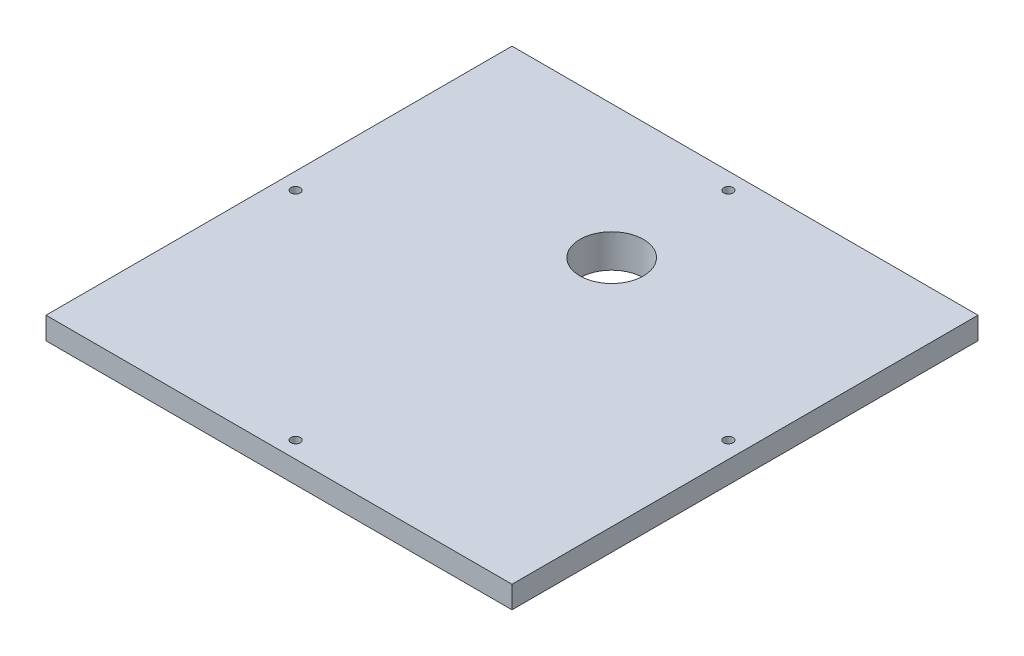
SolidWorks part; units mm, degrees
ref_plane "Front Plane" through (0, 0, 0) normal (0, 0, 1) x (1, 0, 0)
ref_plane "Top Plane" through (0, 0, 0) normal (0, 1, 0) x (1, 0, 0)
ref_plane "Right Plane" through (0, 0, 0) normal (1, 0, 0) x (0, 0, -1)
sketch "Sketch2" plane through (0, 0, 0) normal (0, 1, 0) x (1, 0, 0)
  line L1 (-105, -105) -> (105, -105)
  line L2 (-105, -105) -> (-105, 105)
  line L3 (-105, 105) -> (105, 105)
  line L4 (105, -105) -> (105, 105)
  line L5 (-105, -105) -> (105, 105) construction
  line L6 (-105, 105) -> (105, -105) construction
  point P0 (0, 0)
  dimension "D1" = 210
  dimension "D2" = 210
extrude "Boss-Extrude1" add sketch "Sketch2" along normal blind 10
sketch "Sketch3" plane through (0, 0, 0) normal (0, -1, 0) x (1, 0, 0)
  line L1 (-90, -90) -> (90, -90)
  line L2 (-90, -90) -> (-90, 90)
  line L3 (-90, 90) -> (90, 90)
  line L4 (90, -90) -> (90, 90)
  line L5 (-90, -90) -> (90, 90) construction
  line L6 (-90, 90) -> (90, -90) construction
  point P0 (0, 0)
  dimension "D1" = 180
  dimension "D2" = 180
extrude "Boss-Extrude2" add sketch "Sketch3" along normal blind 5 draft 1
sketch "Sketch4" plane through (0, 10, 0) normal (0, 1, 0) x (1, 0, 0)
  line L0 (-89.9127, 89.9127) -> (89.9127, 89.9127) construction
  circle A0 centre (0, 44.9127) radius 14.3
  point P3 (0, 0)
  point P4 (0, 0)
  point P6 (0, 0)
  dimension "D1" = 28.6
  dimension "D2" = 45
extrude "Cut-Extrude1" cut sketch "Sketch4" against normal up to surface (15 mm away) up to face at (0, -5, 0)
sketch "Sketch6" plane through (0, 10, 0) normal (0, 1, 0) x (1, 0, 0)
  line L0 (105, 105) -> (-105, 105) construction
  circle A0 centre (0, 97.5) radius 2.1
  circle A1 centre (97.5, 0) radius 2.1
  circle A2 centre (0, -97.5) radius 2.1
  circle A3 centre (-97.5, 0) radius 2.1
  dimension "D1" = 4.2
  dimension "D2" = 7.5
  dimension "D3" = 4
extrude "Cut-Extrude2" cut sketch "Sketch6" against normal up to surface (10 mm away) contours A2 | A3 | A0 | A1 region at (0, 10, -97.5) region at (97.5, 10, 0) region at (0, 10, 97.5) region at (-97.5, 10, 0) up to face at (0, 0, 0)
